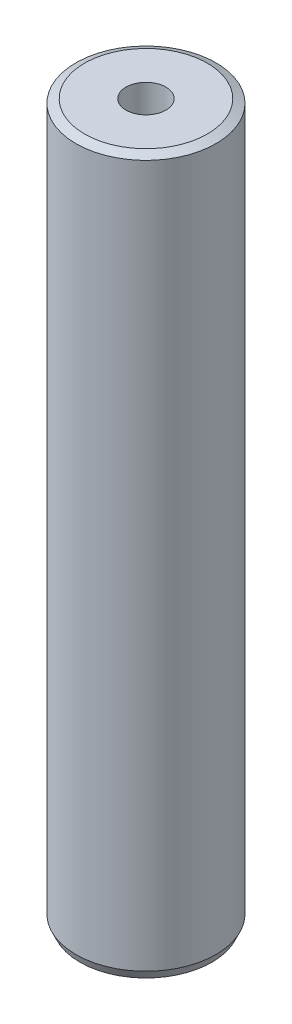
SolidWorks part; units mm, degrees
ref_plane "Front Plane" through (0, 0, 0) normal (0, 0, 1) x (1, 0, 0)
ref_plane "Top Plane" through (0, 0, 0) normal (0, 1, 0) x (1, 0, 0)
ref_plane "Right Plane" through (0, 0, 0) normal (1, 0, 0) x (0, 0, -1)
sketch "Sketch1" plane through (0, 0, 0) normal (0, 1, 0) x (1, 0, 0)
  circle A0 centre (0, 0) radius 5
  dimension "SHAFT_OD" = 10
extrude "Boss-Extrude1" add sketch "Sketch1" along normal blind 51.024
sketch "Sketch2" plane through (0, 0, 0) normal (0, 1, 0) x (1, 0, 0)
  circle A0 centre (0, 0) radius 1.4253
  dimension "BORE_D" = 2.8507
extrude "Cut-Extrude1" cut sketch "Sketch2" along normal through all
chamfer "Chamfer1" distance 0.2847 angle 65.26 2 edges at (0, 51.024, 5) (0, 0, 5) first distance on face at (0, 51.024, 5) first distance on face at (0, 0, 1.4253)
